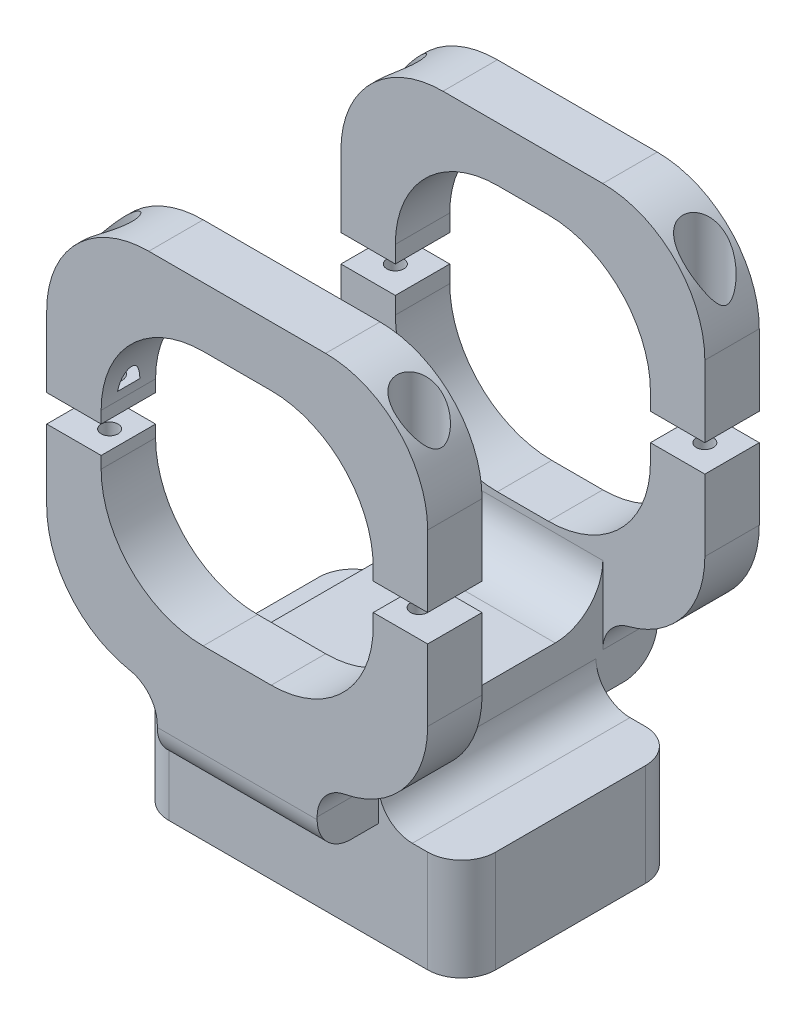
SolidWorks part; units mm, degrees
ref_plane "Front Plane" through (0, 0, 0) normal (0, 0, 1) x (1, 0, 0)
ref_plane "Top Plane" through (0, 0, 0) normal (0, 1, 0) x (1, 0, 0)
ref_plane "Right Plane" through (0, 0, 0) normal (1, 0, 0) x (0, 0, -1)
sketch "Sketch1" plane through (0, 0, 0) normal (0, 0, 1) x (1, 0, 0)
  line L1 (-18.75, 19.5) -> (18.75, 19.5)
  line L2 (-18.75, 19.5) -> (-18.75, -19.5)
  line L3 (-18.75, -19.5) -> (18.75, -19.5)
  line L4 (18.75, 19.5) -> (18.75, -19.5)
  line L5 (-18.75, 19.5) -> (18.75, -19.5) construction
  line L6 (-18.75, -19.5) -> (18.75, 19.5) construction
  line L7 (-26.75, 27.5) -> (26.75, 27.5)
  line L8 (-26.75, 27.5) -> (-26.75, -27.5)
  line L9 (-26.75, -27.5) -> (26.75, -27.5)
  line L10 (26.75, 27.5) -> (26.75, -27.5)
  line L11 (-26.75, 27.5) -> (26.75, -27.5) construction
  line L12 (-26.75, -27.5) -> (26.75, 27.5) construction
  point P0 (0, 0)
  point P6 (0, 0)
  dimension "D1" = 39
  dimension "D2" = 37.5
  dimension "D3" = 8
  dimension "D4" = 8
extrude "Boss-Extrude1" add sketch "Sketch1" along normal blind 8
fillet "Fillet1" radius 15 8 edges at (-18.75, 19.5, 4) (-18.75, -19.5, 4) (18.75, -19.5, 4) (18.75, 19.5, 4) (-26.75, -27.5, 4) (26.75, -27.5, 4) (26.75, 27.5, 4) (-26.75, 27.5, 4)
sketch "Sketch2" plane through (0, -27.5, 0) normal (0, -1, 0) x (1, 0, 0)
  line L0 (11.75, 0) -> (11.75, 8) construction
  line L1 (-11.75, 0) -> (11.75, 0)
  line L2 (-11.75, 0) -> (-11.75, 50)
  line L3 (-11.75, 50) -> (11.75, 50)
  line L4 (11.75, 0) -> (11.75, 50)
  dimension "D1" = 50
extrude "Boss-Extrude2" add sketch "Sketch2" along normal blind 10
sketch "Sketch3" plane through (0, 0, 50) normal (0, 0, 1) x (1, 0, 0)
  line L0 (11.75, -27.5) -> (-11.75, -27.5) construction
  line L1 (-20, 18.75) -> (20, 18.75)
  line L2 (-20, 18.75) -> (-20, -18.75)
  line L3 (-20, -18.75) -> (20, -18.75)
  line L4 (20, 18.75) -> (20, -18.75)
  line L5 (-20, 18.75) -> (20, -18.75) construction
  line L6 (-20, -18.75) -> (20, 18.75) construction
  line L7 (-28, 27.5) -> (28, 27.5)
  line L8 (-28, 27.5) -> (-28, -27.5)
  line L9 (-28, -27.5) -> (28, -27.5)
  line L10 (28, 27.5) -> (28, -27.5)
  line L11 (-28, 27.5) -> (28, -27.5) construction
  line L12 (-28, -27.5) -> (28, 27.5) construction
  point P0 (0, 0)
  point P6 (0, 0)
  dimension "D1" = 40
  dimension "D2" = 37.5
  dimension "D4" = 8
extrude "Boss-Extrude3" add sketch "Sketch3" against normal blind 8
fillet "Fillet2" radius 15 8 edges at (-28, -27.5, 46) (28, -27.5, 46) (28, 27.5, 46) (-28, 27.5, 46) (-20, -18.75, 46) (20, -18.75, 46) (20, 18.75, 46) (-20, 18.75, 46)
fillet "Fillet3" radius 7 2 edges at (0, -27.5, 42) (0, -27.5, 8)
fillet "Fillet4" radius 5 4 edges at (11.75, -27.5, 4) (11.75, -27.5, 46) (-11.75, -27.5, 4) (-11.75, -27.5, 46)
sketch "Sketch4" plane through (0, -37.5, 0) normal (0, -1, 0) x (1, 0, 0)
  line L0 (-11.75, 0) -> (11.75, 0) construction
  line L1 (-24, 41) -> (24, 41)
  line L2 (-24, 41) -> (-24, 9)
  line L3 (-24, 9) -> (24, 9)
  line L4 (24, 41) -> (24, 9)
  line L5 (-24, 41) -> (24, 9) construction
  line L6 (-24, 9) -> (24, 41) construction
  point P0 (0, 25)
  dimension "D1" = 25
  dimension "D2" = 32
  dimension "D3" = 48
extrude "Boss-Extrude4" add sketch "Sketch4" along normal blind 15
fillet "Fillet5" radius 5 4 edges at (24, -45, 9) (24, -45, 41) (-24, -45, 9) (-24, -45, 41)
fillet "Fillet6" radius 5 4 edges at (-11.75, -37.5, 25) (11.75, -37.5, 25) (0, -37.5, 0) (0, -37.5, 50)
hole_wizard "Ø2.5mm Dowel Hole1" positions "Sketch5" profile "Sketch7" hole size "Ø2.5" standard "ANSI Metric"
sketch "Sketch5" plane through (0, -52.5, 0) normal (0, -1, 0) x (-1, 0, 0)
  line L0 (-21, -25) -> (21, -25) construction
  circle A0 centre (0, -25) radius 14 construction
  circle A1 centre (0, -25) radius 21 construction
  point P0 (-14, -25)
  point P2 (14, -25)
  point P4 (21, -25)
  point P6 (-21, -25)
  point P20 (0, 0)
  point P21 (0, 0)
  dimension "D1" = 28
  dimension "D2" = 42
sketch "Sketch7" plane through (14, -52.5, 25) normal (1, 0, 0) x (0, 0, -1)
  line L0 (0, 0) -> (0, 12.7511)
  line L1 (0, 12.7511) -> (1.25, 12)
  line L2 (1.25, 12) -> (1.25, 0)
  line L5 (1.25, 0) -> (0, 0)
  line L10 (0, 12.7511) -> (-1.25, 12) construction
  line L11 (0, -6.35) -> (0, 107.95) construction
  dimension "Hole Dia." = 2.5
  dimension "Hole Depth" = 12
  dimension "Drill Angle" = 118
sketch "Sketch8" plane through (0, 0, 0) normal (0, 0, -1) x (-1, 0, 0)
  line L1 (-40.5381, 2) -> (40.5381, 2)
  line L2 (-40.5381, 2) -> (-40.5381, -2)
  line L3 (-40.5381, -2) -> (40.5381, -2)
  line L4 (40.5381, 2) -> (40.5381, -2)
  line L5 (-40.5381, 2) -> (40.5381, -2) construction
  line L6 (-40.5381, -2) -> (40.5381, 2) construction
  point P0 (0, 0)
  dimension "D1" = 4
extrude "Cut-Extrude1" cut sketch "Sketch8" against normal through all
sketch "Sketch9" plane through (0, -2, 0) normal (0, 1, 0) x (1, 0, 0)
  line L0 (-26.75, -4) -> (26.75, -4) construction
  line L1 (-26.75, -8) -> (-26.75, 0) construction
  line L2 (26.75, 0) -> (26.75, -8) construction
  line L3 (-28, -46) -> (28, -46) construction
  line L4 (-28, -50) -> (-28, -42) construction
  line L5 (28, -42) -> (28, -50) construction
  line L6 (26.75, 0) -> (26.75, -8) construction
  circle A0 centre (-22.75, -4) radius 1.25
  circle A1 centre (22.75, -4) radius 1.25
  circle A2 centre (-22.75, -46) radius 1.25
  circle A3 centre (22.75, -46) radius 1.25
  point P20 (0, 0)
  point P21 (0, 0)
  dimension "D3" = 2.5
  dimension "D4" = 2.5
  dimension "D5" = 2.5
  dimension "D6" = 2.5
  dimension "D1" = 4
  dimension "D2" = 4
extrude "Cut-Extrude2" cut sketch "Sketch9" against normal blind 12 and the other way through all
sketch "Sketch10" plane through (0, 2, 0) normal (0, -1, 0) x (1, 0, 0)
  circle A0 centre (-22.75, 46) radius 1.75
  circle A1 centre (22.75, 46) radius 1.75
  circle A2 centre (22.75, 4) radius 1.75
  circle A3 centre (-22.75, 4) radius 1.75
  dimension "D1" = 3.5
  dimension "D2" = 3.5
  dimension "D3" = 3.5
  dimension "D4" = 3.5
extrude "Cut-Extrude3" cut sketch "Sketch10" against normal through all
sketch "Sketch11" plane through (0, 27.5, 0) normal (0, 1, 0) x (1, 0, 0)
  circle A0 centre (-22.75, -4) radius 3.25
  circle A1 centre (22.75, -4) radius 3.25
  circle A2 centre (22.75, -46) radius 3.25
  circle A3 centre (-22.75, -46) radius 3.25
  dimension "D1" = 6.5
  dimension "D2" = 6.5
  dimension "D3" = 6.5
  dimension "D4" = 6.5
extrude "Cut-Extrude4" cut sketch "Sketch11" against normal offset from surface (22.5 mm away) 3 up to face at (-22.75, 2, 2.25)
